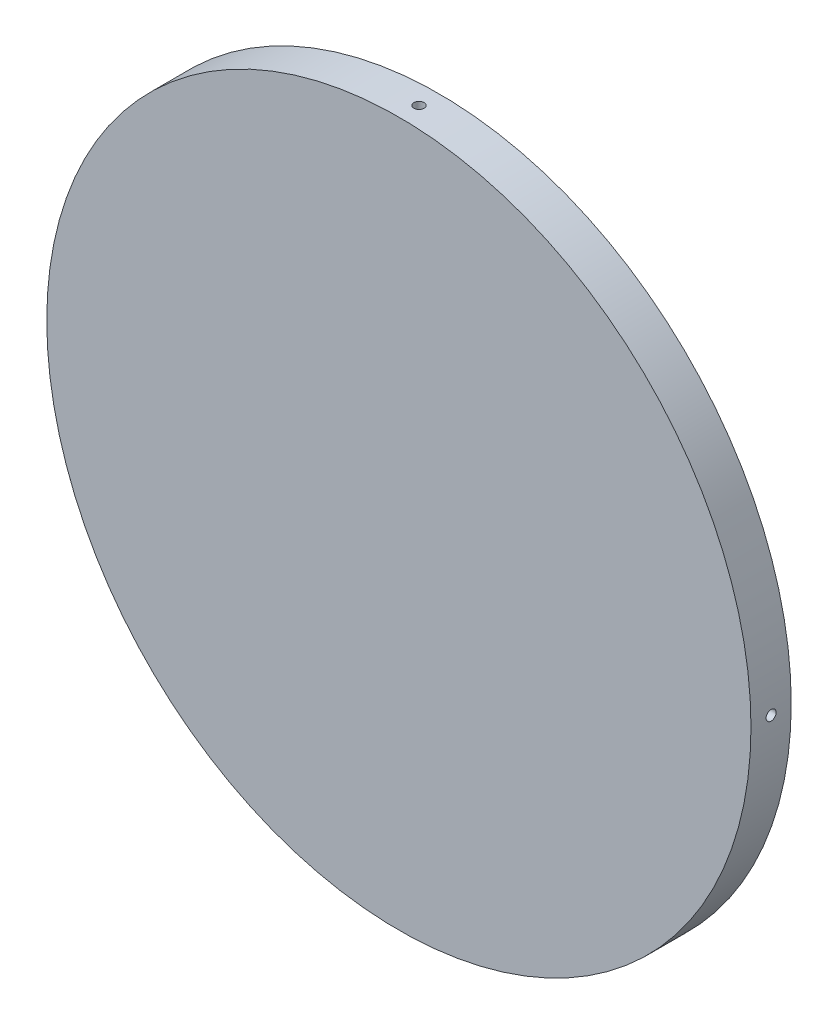
SolidWorks part; units mm, degrees
ref_plane "Front Plane" through (0, 0, 0) normal (0, 0, 1) x (1, 0, 0)
ref_plane "Top Plane" through (0, 0, 0) normal (0, 1, 0) x (1, 0, 0)
ref_plane "Right Plane" through (0, 0, 0) normal (1, 0, 0) x (0, 0, -1)
sketch "Sketch1" plane through (0, 0, 0) normal (0, 0, 1) x (1, 0, 0)
  circle A0 centre (0, 0) radius 70
  dimension "D1" = 140
extrude "Boss-Extrude1" add sketch "Sketch1" along normal blind 8
ref_plane "Plane1" through (0, 70, 0) normal (0, 1, 0) x (1, 0, 0)
sketch "Sketch3" plane through (0, 70, 0) normal (0, 1, 0) x (1, 0, 0)
  line L0 (70, 0) -> (-70, 0) construction
  circle A0 centre (0, -4) radius 1
  dimension "D1" = 2
  dimension "D2" = 4
extrude "Cut-Extrude1" cut sketch "Sketch3" against normal blind 12 contours A0
pattern_circular "CirPattern1" count 4 every 90 about axis through (0, 0, 0) along (0, 0, 1) of "Cut-Extrude1"
